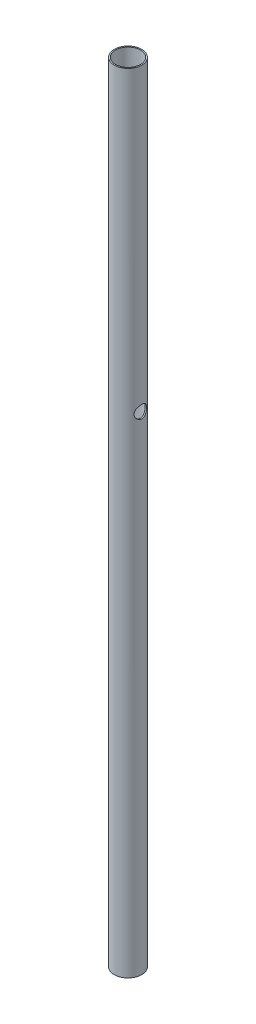
SolidWorks part; units mm, degrees
material "1060 Сплав"
ref_plane "Спереди" through (0, 0, 0) normal (0, 0, 1) x (1, 0, 0)
ref_plane "Сверху" through (0, 0, 0) normal (0, 1, 0) x (1, 0, 0)
ref_plane "Справа" through (0, 0, 0) normal (1, 0, 0) x (0, 0, -1)
sketch "Эскиз1" plane through (0, 0, 0) normal (0, 0, 1) x (1, 0, 0)
  line L0 (0, 0) -> (0, -630)
  dimension "D1" = 630
sketch "Эскиз2" plane through (0, 0, 0) normal (0, 1, 0) x (1, 0, 0)
  circle A0 centre (0, 0) radius 11
  circle A1 centre (0, 0) radius 10
  dimension "D1" = 22
  dimension "D2" = 20
sweep "По траектории1" add profiles "Эскиз2" path "Эскиз1"
sketch "Эскиз3" plane through (0, 0, 0) normal (1, 0, 0) x (0, 0, -1)
  line L0 (0, 0) -> (0, -343.1833) construction
  circle A0 centre (0, -240) radius 5
  dimension "D1" = 10
  dimension "D10" = 240
extrude "Вырез-Вытянуть1" cut sketch "Эскиз3" against normal through all and the other way through all
